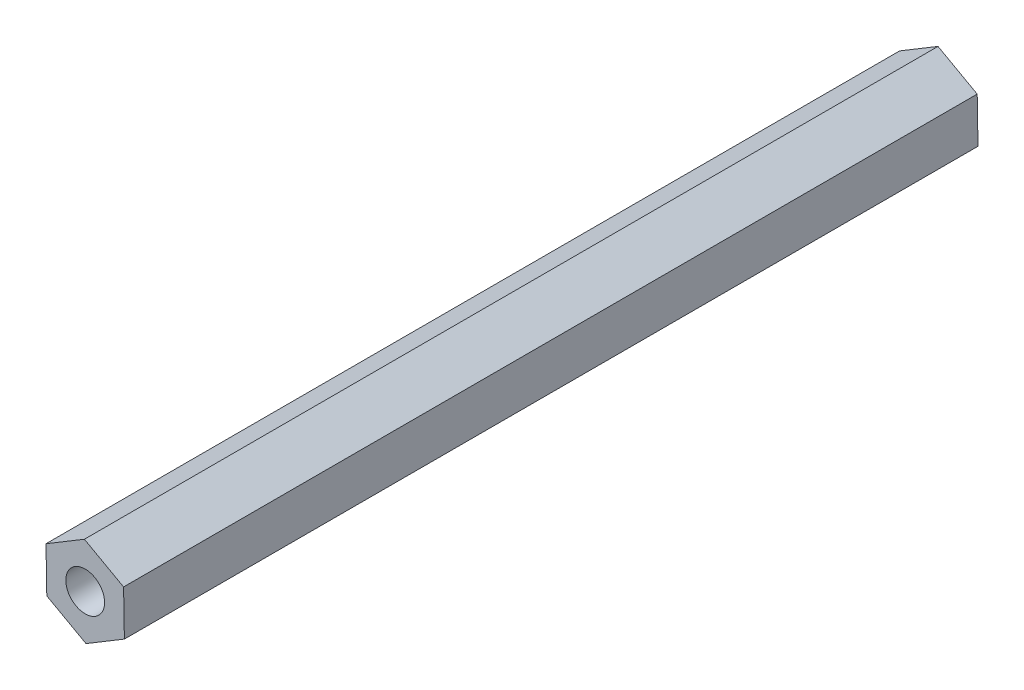
SolidWorks part; units mm, degrees
ref_plane "Front Plane" through (0, 0, 0) normal (0, 0, 1) x (1, 0, 0)
ref_plane "Top Plane" through (0, 0, 0) normal (0, 1, 0) x (1, 0, 0)
ref_plane "Right Plane" through (0, 0, 0) normal (1, 0, 0) x (0, 0, -1)
sketch "Sketch1" plane through (0, 0, 0) normal (0, 0, 1) x (1, 0, 0)
  line L1 (6.2843, 3.7777) -> (-0.1294, 7.3312)
  line L2 (-0.1294, 7.3312) -> (-6.4137, 3.5536)
  line L3 (-6.4137, 3.5536) -> (-6.2843, -3.7777)
  line L4 (-6.2843, -3.7777) -> (0.1294, -7.3312)
  line L5 (0.1294, -7.3312) -> (6.4137, -3.5536)
  line L6 (6.4137, -3.5536) -> (6.2843, 3.7777)
  circle A0 centre (0, 0) radius 6.35 construction
  circle A1 centre (0, 0) radius 3.175
  dimension "D1" = 12.7
extrude "Boss-Extrude1" add sketch "Sketch1" along normal blind 69.85 and the other way blind 69.85
